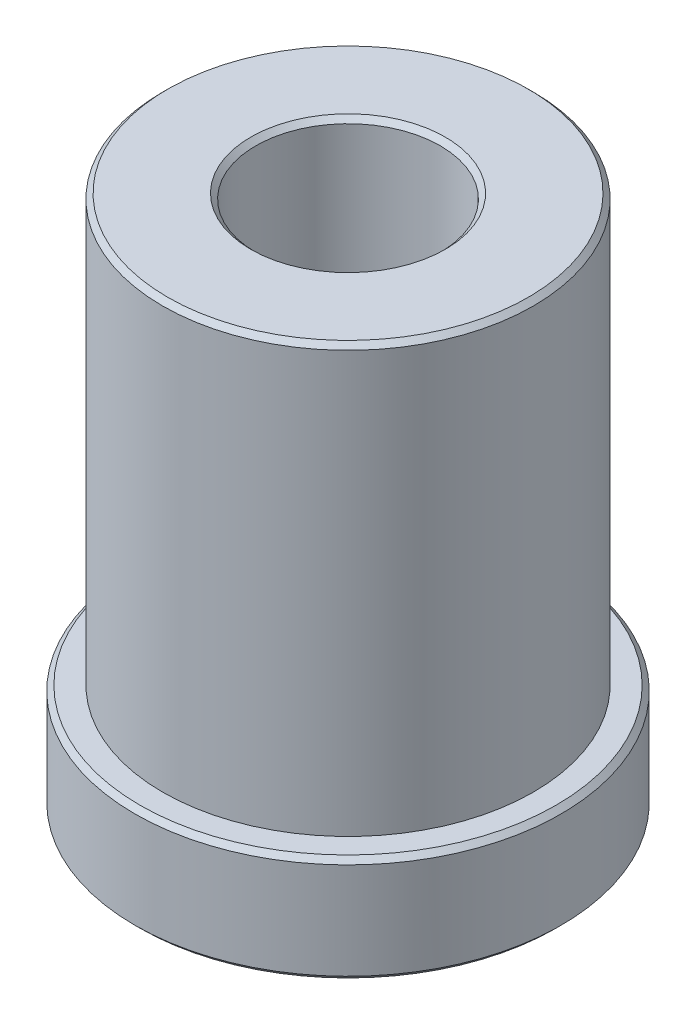
SolidWorks part; units mm, degrees
material "Nylon 101"
ref_plane "Front Plane" through (0, 0, 0) normal (0, 0, 1) x (1, 0, 0)
ref_plane "Top Plane" through (0, 0, 0) normal (0, 1, 0) x (1, 0, 0)
ref_plane "Right Plane" through (0, 0, 0) normal (1, 0, 0) x (0, 0, -1)
sketch "Sketch1" plane through (0, 0, 0) normal (0, 1, 0) x (1, 0, 0)
  circle A0 centre (0, 0) radius 11.049
  dimension "D1" = 22.098
extrude "Boss-Extrude1" add sketch "Sketch1" along normal blind 25.4
sketch "Sketch2" plane through (0, 0, 0) normal (0, -1, 0) x (1, 0, 0)
  circle A0 centre (0, 0) radius 12.7
  dimension "D1" = 25.4
extrude "Boss-Extrude2" add sketch "Sketch2" along normal blind 6.35
sketch "Sketch3" plane through (0, -6.35, 0) normal (0, -1, 0) x (1, 0, 0)
  circle A0 centre (0, 0) radius 5.5
  dimension "D1" = 11
extrude "Cut-Extrude1" cut sketch "Sketch3" against normal through all
sketch "Sketch4" plane through (0, -6.35, 0) normal (0, -1, 0) x (1, 0, 0)
  circle A0 centre (0, 0) radius 11.1125
  dimension "D1" = 22.225
ref_plane "Plane1" through (0, 9.525, 0) normal (0, 1, 0) x (1, 0, 0)
chamfer "Chamfer1" distance 0.3 angle 45 5 edges at (0, 0, -12.7) (0, -6.35, -12.7) (0, 25.4, 11.049) (0, 25.4, -5.5) (0, -6.35, -5.5)
equation "\"D1@Chamfer1\"=.3mm"
